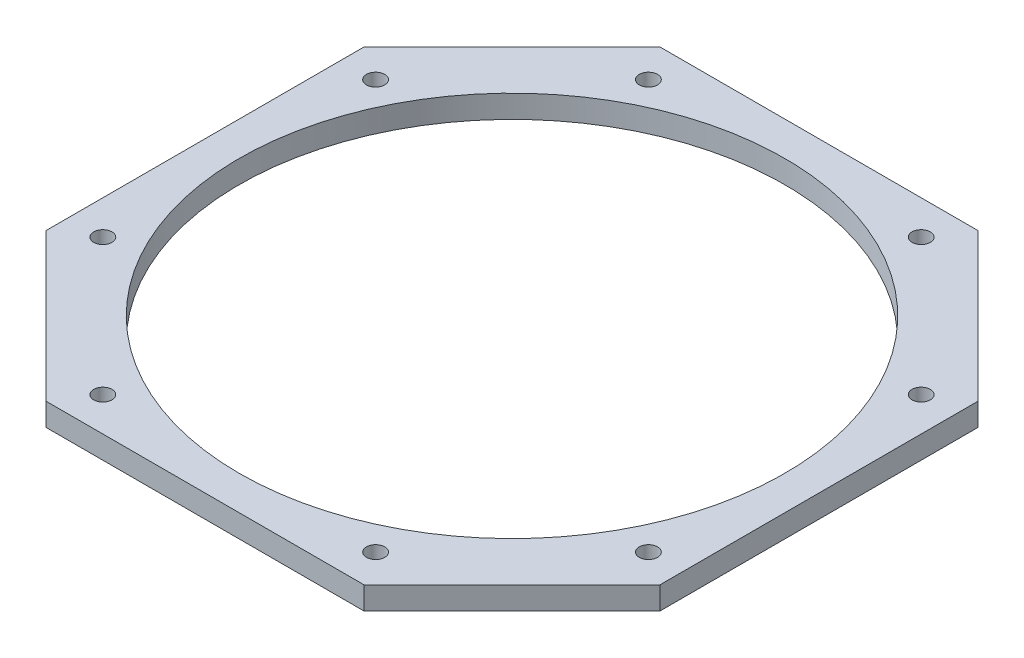
SolidWorks part; units mm, degrees
ref_plane "Front Plane" through (0, 0, 0) normal (0, 0, 1) x (1, 0, 0)
ref_plane "Top Plane" through (0, 0, 0) normal (0, 1, 0) x (1, 0, 0)
ref_plane "Right Plane" through (0, 0, 0) normal (1, 0, 0) x (0, 0, -1)
sketch "Sketch1" plane through (0, 0, 0) normal (0, 1, 0) x (1, 0, 0)
  line L0 (-85.725, 44.45) -> (-44.45, 85.725)
  line L1 (-44.45, -85.725) -> (44.45, -85.725)
  line L2 (-85.725, -44.45) -> (-85.725, 44.45)
  line L3 (-44.45, 85.725) -> (44.45, 85.725)
  line L4 (85.725, -44.45) -> (85.725, 44.45)
  line L5 (-85.725, -85.725) -> (85.725, 85.725) construction
  line L6 (-85.725, 85.725) -> (85.725, -85.725) construction
  line L7 (44.45, 85.725) -> (85.725, 44.45)
  line L8 (85.725, -44.45) -> (44.45, -85.725)
  line L9 (-85.725, -44.45) -> (-44.45, -85.725)
  point P0 (0, 0)
  dimension "D1" = 171.45
  dimension "D2" = 171.45
  dimension "D3" = 88.9
extrude "Boss-Extrude1" add sketch "Sketch1" along normal blind 6.35
hole_wizard "#7 (0.201) Diameter Hole1" positions "Sketch3" profile "Sketch2" hole size "#7" standard "Ansi Inch" end condition through all
sketch "Sketch3" plane through (0, 6.35, 0) normal (0, 1, 0) x (-1, 0, 0)
  line L0 (-38.1, -76.2) -> (0, 0) construction
  line L1 (0, 0) -> (38.1, -76.2) construction
  line L4 (-44.45, -85.725) -> (44.45, -85.725) construction
  point P0 (38.1, -76.2)
  point P1 (-38.1, -76.2)
  dimension "D1" = 76.2
  dimension "D2" = 9.525
sketch "Sketch2" plane through (-38.1, 6.35, -76.2) normal (1, 0, 0) x (0, 0, 1)
  line L0 (0, 0) -> (0, 6.35)
  line L1 (0, 6.35) -> (2.5527, 6.35)
  line L2 (2.5527, 6.35) -> (2.5527, 0)
  line L5 (2.5527, 0) -> (0, 0)
  line L11 (0, -6.35) -> (0, 107.95) construction
  dimension "Thru Hole Dia." = 5.1054
  dimension "Thru Hole Depth" = 6.35
ref_axis "Axis1" through (0, 0, 0) along (0, 1, 0)
pattern_circular "CirPattern1" count 4 over 360 about axis through (0, 0, 0) along (0, 1, 0) of "#7 (0.201) Diameter Hole1"
sketch "Sketch4" plane through (0, 6.35, 0) normal (0, 1, 0) x (1, 0, 0)
  circle A0 centre (0, 0) radius 76.2
  dimension "D1" = 152.4
extrude "Cut-Extrude1" cut sketch "Sketch4" against normal through all
